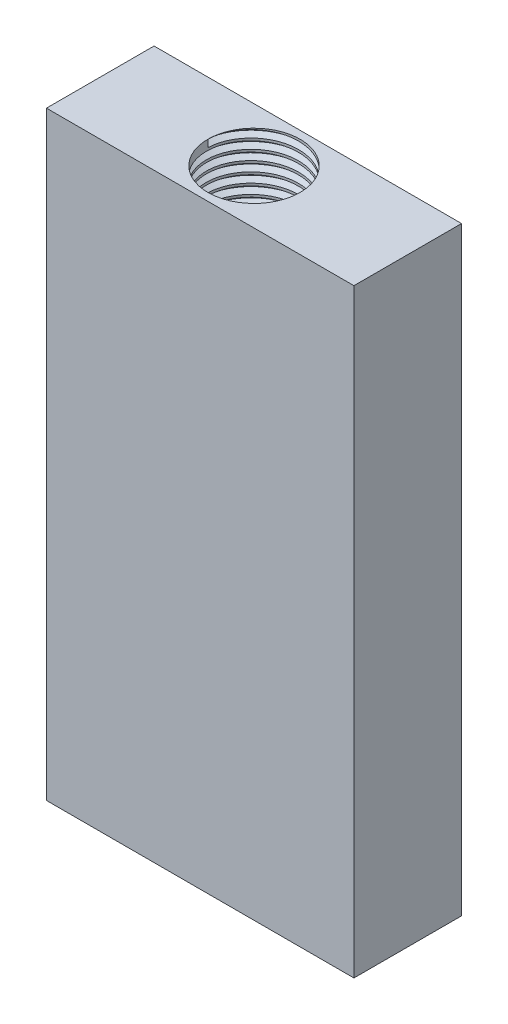
SolidWorks part; units mm, degrees
ref_plane "Front Plane" through (0, 0, 0) normal (0, 0, 1) x (1, 0, 0)
ref_plane "Top Plane" through (0, 0, 0) normal (0, 1, 0) x (1, 0, 0)
ref_plane "Right Plane" through (0, 0, 0) normal (1, 0, 0) x (0, 0, -1)
sketch "Sketch2" plane through (0, 0, 0) normal (0, 0, 1) x (1, 0, 0)
  line L8 (-5, -27.35) -> (5, -27.35)
  line L9 (-5, -27.35) -> (-5, -7.85)
  line L10 (-5, -7.85) -> (5, -7.85)
  line L11 (5, -27.35) -> (5, -7.85)
  line L12 (-5, -27.35) -> (5, -7.85) construction
  line L13 (-5, -7.85) -> (5, -27.35) construction
  point P0 (0, 0)
  point P8 (0, -17.6)
  dimension "D6" = 19.5
  dimension "D7" = 10
extrude "Boss-Extrude1" add sketch "Sketch2" along normal blind 3.5 contours L8 L11 L9 region at (0, -17.6, 0)
sketch "Sketch11" plane through (0, -7.85, 0) normal (0, 1, 0) x (1, 0, 0)
  line L0 (0, 0) -> (0, -4.4101) construction
  line L2 (-5, -1.75) -> (6.9613, -1.75) construction
  line L3 (-5, -3.5) -> (-5, 0) construction
  circle A1 centre (0, -1.75) radius 1.5
  dimension "D1" = 3
extrude "Cut-Extrude1" cut sketch "Sketch11" against normal blind 3.5
thread "Thread1" pitch 0.3175 method cut profile "Thread Profile1" start angle 0, offset 0, length 3.5, pitch 0.3175, diameter 3
ref_plane "Plane1" through (-1.5, -7.85, 1.75) normal (0, 0, 1) x (-1, 0, 0)
sketch "Thread Profile1" plane through (-1.5, -7.85, 1.75) normal (0, 0, 1) x (-1, 0, 0)
  line L0 (0, 0) -> (0, 0.3175) construction
  line L1 (0, 0) -> (0.1719, 0.0992)
  line L2 (0.1719, 0.0992) -> (0.1719, 0.1389)
  line L3 (0.1719, 0.1389) -> (0, 0.2381)
  line L4 (0.1719, 0.1191) -> (0, 0.1191) construction
  line L11 (0, 0) -> (0, 0.2381)
  point P2 (0, 0)
  dimension "Pitch" = 0.3175
  dimension "Profile_Angle" = 60
  dimension "Profile_Land" = 0.0397
  dimension "Profile_Height" = 0.1719
sketch "Sketch15" plane through (0, -27.35, 0) normal (0, -1, 0) x (-1, 0, 0)
  line L0 (0, 0) -> (0, -5.5713) construction
  line L1 (5, -1.75) -> (-5.3339, -1.75) construction
  line L2 (5, -3.5) -> (5, 0) construction
  circle A0 centre (0, -1.75) radius 1.5
  dimension "D1" = 3
extrude "Cut-Extrude2" cut sketch "Sketch15" against normal blind 3.5
thread "Thread2" pitch 0.3175 method cut profile "Thread Profile2" start angle 0, offset 0, length 3.5, pitch 0.3175, diameter 3
ref_plane "Plane2" through (1.5, -27.35, 1.75) normal (0, 0, 1) x (1, 0, 0)
sketch "Thread Profile2" plane through (1.5, -27.35, 1.75) normal (0, 0, 1) x (1, 0, 0)
  line L0 (0, 0) -> (0, 0.3175) construction
  line L1 (0, 0) -> (0.1719, 0.0992)
  line L2 (0.1719, 0.0992) -> (0.1719, 0.1389)
  line L3 (0.1719, 0.1389) -> (0, 0.2381)
  line L4 (0.1719, 0.1191) -> (0, 0.1191) construction
  line L11 (0, 0) -> (0, 0.2381)
  point P2 (0, 0)
  dimension "Pitch" = 0.3175
  dimension "Profile_Angle" = 60
  dimension "Profile_Land" = 0.0397
  dimension "Profile_Height" = 0.1719
